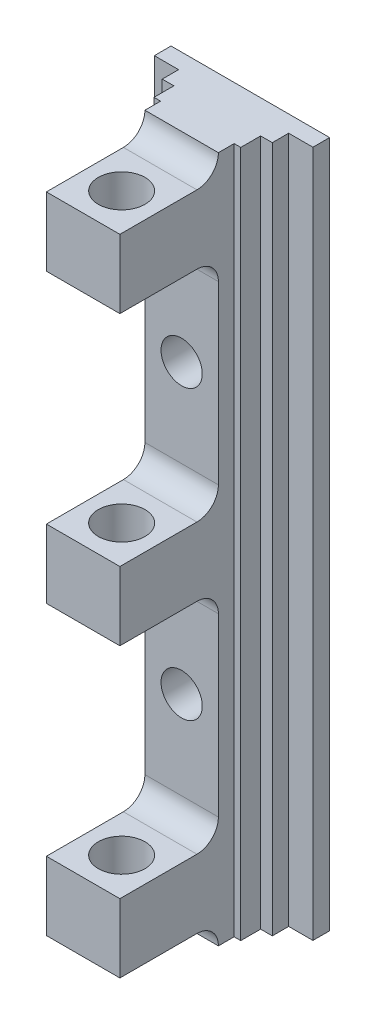
SolidWorks part; units mm, degrees
ref_plane "Front Plane" through (0, 0, 0) normal (0, 0, 1) x (1, 0, 0)
ref_plane "Top Plane" through (0, 0, 0) normal (0, 1, 0) x (1, 0, 0)
ref_plane "Right Plane" through (0, 0, 0) normal (1, 0, 0) x (0, 0, -1)
sketch "Sketch1" plane through (0, 0, 0) normal (0, 1, 0) x (1, 0, 0)
  line L0 (-2.7178, 2.54) -> (2.7178, -2.54) construction
  line L1 (-2.7178, 2.54) -> (2.7178, 2.54)
  line L2 (-2.7178, 2.54) -> (-2.7178, -2.54)
  line L4 (2.7178, 2.54) -> (2.7178, -2.54)
  line L6 (-2.7178, -2.54) -> (2.7178, -2.54)
  point P1 (-2.6925, -2.3044)
  point P4 (0, 0)
  point P6 (0, 0)
  point P9 (2.7178, -2.4463)
  point P11 (1.0926, -0.635)
  point P12 (2.4937, -1.4295)
  point P13 (0, 0)
  point P14 (1.9945, -2.2335)
  point P15 (0, 0)
  dimension "D2" = 5.08
  dimension "D3" = 5.4356
extrude "Boss-Extrude1" add sketch "Sketch1" against normal blind 50.8
ref_plane "midplane" through (0, -25.4, 0) normal (0, 1, 0) x (1, 0, 0)
sketch "Sketch3" plane through (0, 0, 0) normal (0, 1, 0) x (1, 0, 0)
  line L0 (2.7178, 2.54) -> (-2.7178, 2.54) construction
  line L1 (-1.5875, 5.207) -> (1.5875, 5.207)
  line L2 (-1.5875, 5.207) -> (-1.5875, 2.54)
  line L3 (-1.5875, 2.54) -> (1.5875, 2.54)
  line L4 (1.5875, 5.207) -> (1.5875, 2.54)
  point P6 (0, 2.54)
  dimension "D1" = 3.175
  dimension "D2" = 2.667
extrude "Boss-Extrude2" [suppressed] add sketch "Sketch3" against normal up to surface (50.8 mm away)
ref_plane "Plane2" through (0, -1.5875, 0) normal (0, 1, 0) x (1, 0, 0)
sketch "Sketch4" plane through (0, -1.5875, 0) normal (0, 1, 0) x (1, 0, 0)
  line L1 (-2.7178, -9.824) -> (2.7178, -9.824)
  line L2 (-2.7178, -9.824) -> (-2.7178, -2.54)
  line L3 (-2.7178, -2.54) -> (2.7178, -2.54)
  line L4 (2.7178, -9.824) -> (2.7178, -2.54)
  point P4 (2.8289, -4.445)
  point P5 (-2.7178, -4.445)
  point P6 (-2.3316, -4.3334)
  point P7 (0, 0)
  point P10 (0, 0)
  dimension "D1" = 7.284
extrude "Boss-Extrude3" add sketch "Sketch4" against normal blind 5.08
sketch "Sketch13" plane through (2.7178, 0, 0) normal (1, 0, 0) x (0, 0, -1)
  line L0 (-9.824, -6.6675) -> (-9.824, -1.5875) construction
  line L1 (-9.824, -27.94) -> (-2.54, -27.94)
  line L2 (-9.824, -27.94) -> (-9.824, -22.86)
  line L3 (-9.824, -22.86) -> (-2.54, -22.86)
  line L4 (-2.54, -27.94) -> (-2.54, -22.86)
  line L5 (-2.54, -50.8) -> (-2.54, -6.6675) construction
  line L6 (2.794, -25.4) -> (-2.794, -25.4) construction
  point P8 (-2.54, -25.4)
extrude "Boss-Extrude6" add sketch "Sketch13" against normal up to surface (5.4356 mm away) up to face at (-2.7178, -14.7637, 3.091)
fillet "Fillet1" radius 1.5875 4 edges at (0, -6.6675, 2.54) (0, -1.5875, 2.54) (0, -27.94, 2.54) (0, -22.86, 2.54)
hole_wizard "#4 Clearance Hole1" positions "Sketch5" profile "Sketch6" hole size "#4" standard "ANSI Inch" end condition through all
sketch "Sketch5" plane through (0, 0, 0) normal (0, 1, 0) x (1, 0, 0)
  line L0 (0, -9.824) -> (0, -4.1275) construction
  line L1 (-2.7178, -9.824) -> (2.7178, -9.824) construction
  line L3 (-2.7178, -4.1275) -> (2.7178, -4.1275) construction
  point P0 (0, -6.9757)
sketch "Sketch6" plane through (0, 0, 6.9757) normal (1, 0, 0) x (0, 0, 1)
  line L0 (0, 0) -> (0, 50.8)
  line L1 (0, 50.8) -> (1.7272, 50.8)
  line L2 (1.7272, 50.8) -> (1.7272, 0)
  line L5 (1.7272, 0) -> (0, 0)
  line L11 (0, -6.35) -> (0, 107.95) construction
  dimension "Thru Hole Dia." = 3.4544
  dimension "Thru Hole Depth" = 50.8
mirror "Mirror5" about plane through (0, -25.4, 0) normal (0, 1, 0) of "Boss-Extrude3", "Fillet1", "#4 Clearance Hole1"
sketch "Sketch7" plane through (0, 0, 0) normal (0, 1, 0) x (1, 0, 0)
  line L0 (3.2076, -1.3765) -> (3.2076, 0.0954)
  line L1 (2.7178, 2.54) -> (2.7178, -1.3765)
  line L2 (2.7178, -2.54) -> (2.7178, 2.54) construction
  line L3 (2.7178, 2.54) -> (5.8632, 2.54)
  line L4 (3.2076, 0.0954) -> (4.0696, 0.0954)
  line L5 (4.0696, 0.0954) -> (4.0696, 1.3049)
  line L6 (4.0696, 1.3049) -> (5.8632, 1.3049)
  line L7 (5.8632, 1.3049) -> (5.8632, 2.54)
  line L8 (2.7178, -1.3765) -> (3.2076, -1.3765)
  arc A0 (8.128, 2.1717) -> (2.7181, -2.3962) centre (7.6343, -2.7311) ccw construction
  arc A1 (8.128, 2.1717) -> (2.7178, -2.401) centre (7.6343, -2.7311) ccw construction
  circle A2 centre (0, -78.5477) radius 81.8896 construction
  circle A3 centre (0, -78.5477) radius 81.8896 construction
  point P0 (5.8632, 1.3049)
extrude "Boss-Extrude4" add sketch "Sketch7" against normal up to surface (50.8 mm away) up to face at (0, -50.8, 0)
ref_plane "Plane3" through (0, 0, 0) normal (1, 0, 0) x (0, 0, -1)
mirror "Mirror6" about plane through (0, 0, 0) normal (1, 0, 0) of "Boss-Extrude4"
hole_wizard "Tapped Hole for #4-40 Helicoil1" positions "Sketch10" profile "Sketch11" tap size "#4-40" standard "Helicoil® Inch"
sketch "Sketch10" plane through (0, 0, -2.54) normal (0, 0, -1) x (-1, 0, 0)
  line L0 (2.7178, -6.6675) -> (-2.7178, -1.5875) construction
  line L2 (5.8632, -25.4) -> (-5.8632, -25.4) construction
  line L4 (5.8632, -50.8) -> (5.8632, 0) construction
  line L5 (-5.8632, -50.8) -> (-5.8632, 0) construction
  line L6 (0, -8.255) -> (0, -21.2725) construction
  line L8 (-2.7178, -8.255) -> (2.7178, -8.255) construction
  line L9 (2.7178, -21.2725) -> (-2.7178, -21.2725) construction
  point P0 (0, -4.1275)
  point P24 (0, -46.6725)
  point P25 (0, -25.4)
  point P46 (0, -14.7637)
  point P49 (0, 0)
  point P50 (0, -36.0362)
cosmetic thread "Hole Thread1" parameters "D1"=3.556, "D2"=3.7414
cosmetic thread "Hole Thread2" parameters "D1"=3.556, "D2"=3.7414
sketch "Sketch11" plane through (0, -4.1275, -2.54) normal (1, 0, 0) x (0, 1, 0)
  line L0 (0, 0) -> (0, 5.9957)
  line L1 (0, 5.9957) -> (1.524, 5.08)
  line L2 (1.524, 5.08) -> (1.524, 0)
  line L5 (1.524, 0) -> (0, 0)
  line L10 (0, 5.9957) -> (-1.524, 5.08) construction
  line L11 (0, -6.35) -> (0, 107.95) construction
  dimension "Tap Drill Dia." = 3.048
  dimension "Tap Drill Depth" = 5.08
  dimension "Drill Angle" = 118
cosmetic thread "Hole Thread3" parameters "D1"=3.556, "D2"=3.7414
cosmetic thread "Hole Thread4" parameters "D1"=3.556, "D2"=3.7414
cosmetic thread "Hole Thread5" parameters "D1"=3.556, "D2"=3.7414
